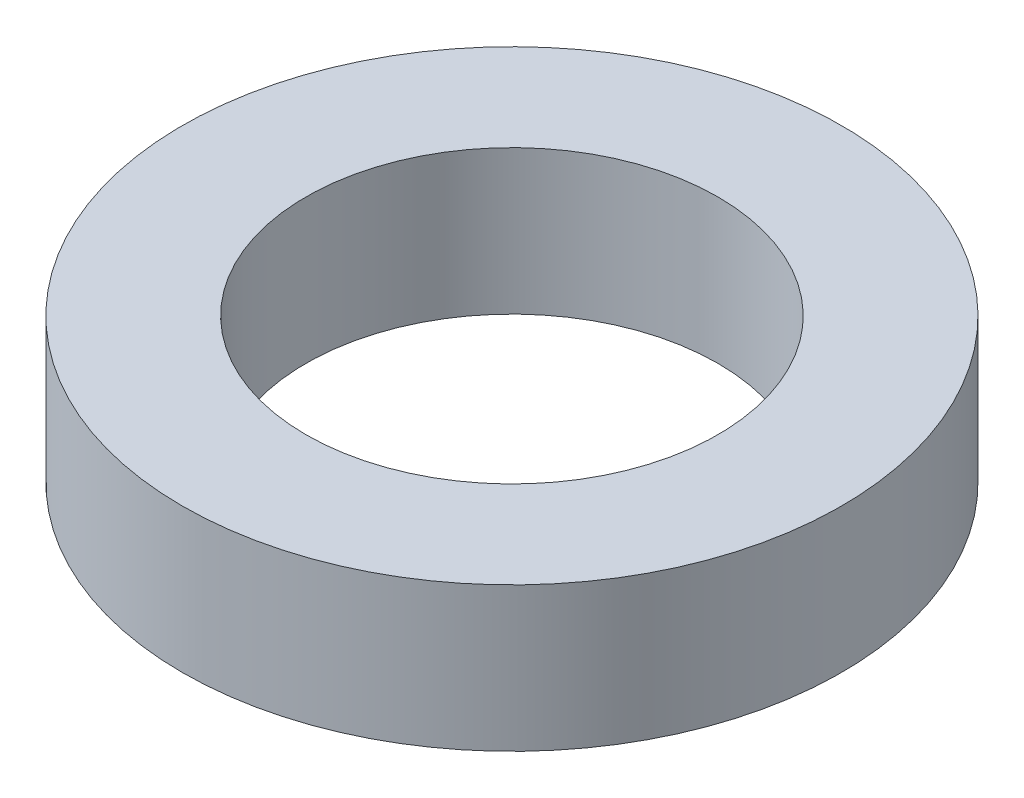
SolidWorks part; units mm, degrees
ref_plane "Front Plane" through (0, 0, 0) normal (0, 0, 1) x (1, 0, 0)
ref_plane "Top Plane" through (0, 0, 0) normal (0, 1, 0) x (1, 0, 0)
ref_plane "Right Plane" through (0, 0, 0) normal (1, 0, 0) x (0, 0, -1)
sketch "Sketch1" plane through (0, 0, 0) normal (0, 1, 0) x (1, 0, 0)
  circle A0 centre (0, 0) radius 16
  circle A1 centre (0, 0) radius 10
  dimension "D1" = 20
  dimension "D2" = 32
extrude "Boss-Extrude1" add sketch "Sketch1" along normal mid plane 7
equation "\"Ns\" = 48"
equation "\"Np_b\" = 40"
equation "\"Np_s\" = 28"
equation "\"Nr_b\" = 128"
equation "\"num_planet\" = 4"
equation "\"module\" = 0.7"
equation "\"fw_p_b\" = 29.99577312706301"
equation "\"fw_r_b\" = 29.99577312706301"
equation "\"fw_s_calc\" = 5.685933367726717"
equation "\"fw_r_s\" = 24.412913082891553"
equation "\"fw_p_s\" = 25.912913082891553"
equation "\"fw_s_used\" = 63.40868620995457"
equation "\"pressure_angle\" = 20.0"
equation "\"motor_OD\" = 106.8"
equation "\"motor_height\" = 47.6"
equation "\"motor_mount_hole_PCD\" = 40"
equation "\"motor_mount_hole_dia\" = 5"
equation "\"motor_mount_hole_num\" = 4"
equation "\"wire_slot_dist_from_center\" = 45.5"
equation "\"wire_slot_length\" = 10"
equation "\"wire_slot_radius\" = 3"
equation "\"motor_output_hole_PCD\" = 23"
equation "\"motor_output_hole_dia\" = 4"
equation "\"motor_output_hole_num\" = 4"
equation "\"h_a\" = 0.7"
equation "\"h_f\" = 0.875"
equation "\"clr_tip_root\" = 0.17500000000000004"
equation "\"dp_r_b\" = 89.6"
equation "\"db_r_b\" = 84.19645882241738"
equation "\"alpha_r_b\" = 0.8539582918412556"
equation "\"beta_r_b\" = 3.114166583682511"
equation "\"bearing_ID\" = 70"
equation "\"bearing_OD\" = 90"
equation "\"bearing_height\" = 10"
equation "\"clearance_planet\" = 1.5"
equation "\"case_dist\" = 6.5"
equation "\"Motor_case_OD_max\" = 131.3"
equation "\"case_mounting_PCD\" = 123.8"
equation "\"bearing mount thickness\" = 8"
equation "\"case_mounting_hole_dia\" = 3"
equation "\"output_mounting_PCD\" = 98"
equation "\"output_mounting_hole_dia\" = 4"
equation "\"clearance_case_mount_holes_shell_thickness\" = 1"
equation "\"motor_case_OD_base\" = 121.8"
equation "\"sec_carrier_thickness\" = 5"
equation "\"sun_coupler_hub_thickness\" = 4"
equation "\"clearance_sun_coupler_sec_carrier\" = 1.5"
equation "\"clearance_motor_and_case\" = 5"
equation "\"Motor_case_thickness\" = 2.5"
equation "\"Motor_case_ID\" = 116.8"
equation "\"case_mounting_hole_shift\" = 1.0"
equation "\"output_mounting_nut_wrench_size\" = 7"
equation "\"output_mounting_nut_thickness\" = 3.2"
equation "\"case_mounting_hole_allen_socket_dia\" = 5.5"
equation "\"output_mounting_nut_depth\" = 3"
equation "\"case_mounting_bolt_depth\" = 4.5"
equation "\"ring_radial_thickness\" = 5"
equation "\"ring_OD_b\" = 99.6"
equation "\"ring_to_chamfer_clearance\" = 1.5"
equation "\"Motor_case_OD_base_to_chamfer\" = 5"
equation "\"pattern_offset_from_motor_case_OD_base\" = 3"
equation "\"pattern_bulge_dia\" = 3"
equation "\"pattern_num_bulge\" = 18"
equation "\"pattern_depth\" = 2"
equation "\"case_mounting_wrench_size\" = 5.5"
equation "\"case_mounting_nut_clearance\" = 2"
equation "\"base_plate_thickness\" = 4"
equation "\"case_mounting_nut_thickness\" = 2.4"
equation "\"case_mounting_surface_height\" = 4"
equation "\"central_hole_offset_from_motor_mount_PCD\" = 5"
equation "\"driver_upper_holes_dist_from_center\" = 29"
equation "\"driver_lower_holes_dist_from_center\" = 13"
equation "\"driver_side_holes_dist_from_center\" = 22.5"
equation "\"driver_mount_holes_dia\" = 3"
equation "\"driver_mount_inserts_OD\" = 4.8"
equation "\"driver_mount_thickness\" = 1.5"
equation "\"driver_mount_height\" = 6"
equation "\"air_flow_hole_offset\" = 3"
equation "\"pressure angle\" = 20.0"
equation "\"h_b\" = 0.875"
equation "\"planet_pin_bolt_dia\" = 5"
equation "\"planet_pin_socket_head_dia\" = 8.5"
equation "\"carrier_PCD\" = 61.599999999999994"
equation "\"planet_shaft_dia\" = 8"
equation "\"planet_shaft_step_offset\" = 1"
equation "\"carrier_trapezoidal_support_sun_offset\" = 5"
equation "\"carrier_trapezoidal_support_hole_PCD_offset_bearing_ID\" = 4"
equation "\"carrier_trapezoidal_support_hole_dia\" = 3"
equation "\"carrier_trapezoidal_support_hole_socket_head_dia\" = 5.5"
equation "\"carrier_bearing_step_width\" = 1.5"
equation "\"standard_clearance_1_5mm\" = 1.5"
equation "\"standard_fillet_1_5mm\" = 1.5"
equation "\"sun_shaft_bearing_ID\" = 8"
equation "\"sun_shaft_bearing_OD\" = 16"
equation "\"sun_shaft_bearing_width\" = 5"
equation "\"standard_bearing_insertion_chamfer\" = 0.5"
equation "\"carrier_trapezoidal_support_hole_wrench_size\" = 5.5"
equation "\"planet_pin_bolt_wrench_size\" = 8"
equation "\"planet_bearing_OD\" = 12"
equation "\"planet_bearing_width\" = 3.5"
equation "\"planet_bore\" = 10"
equation "\"dp_s\" = 33.599999999999994"
equation "\"db_s\" = 31.57367205840652"
equation "\"alpha_s\" = 0.8539582918412343"
equation "\"beta_s\" = 2.0420834163175314"
equation "\"dp_p_b\" = 28.0"
equation "\"db_p_b\" = 26.311393382005434"
equation "\"alpha_p_b\" = 0.8539582918412485"
equation "\"beta_p_b\" = 2.792083416317503"
equation "\"sun_hub_dia\" = 30.0"
equation "\"sun_central_bolt_dia\" = 5"
equation "\"sun_central_bolt_socket_head_dia\" = 8.5"
equation "\"motor_output_hole_CSK_OD\" = 8"
equation "\"motor_output_hole_CSK_head_height\" = 2.0"
equation "\"bearing_retainer_thickness\" = 2"
equation "\"dp_p_s\" = 19.599999999999998"
equation "\"db_p_s\" = 18.417975367403802"
equation "\"alpha_p_s\" = 0.8539582918412592"
equation "\"beta_p_s\" = 4.7206548448889105"
equation "\"Nr_s\" = 116"
equation "\"clr_tip_root_s\" = 0.17500000000000004"
equation "\"dp_r_s\" = 81.19999999999999"
equation "\"db_r_s\" = 76.30304080781575"
equation "\"alpha_r_s\" = 0.8539582918412556"
equation "\"beta_r_s\" = 3.259640721613546"
equation "\"small_ring_case_thickness\" = 4"
equation "\"carrier_thickness\" = 4"
equation "\"small_ring_output_wall_thickness\" = 5"
equation "\"small_ring_output_wall_to_bearing_shaft_attachement_hole_dia\" = 4"
equation "\"small_ring_output_wall_to_bearing_shaft_attachement_hole_depth\" = 6.5"
equation "\"small_ring_output_wall_to_bearing_shaft_attachement_nut_wrench\" = 7"
equation "\"small_ring_output_wall_to_bearing_shaft_attachement_nut_thickness\" = 3.2"
equation "\"small_ring_output_wall_to_bearing_shaft_attachement_hole_pcd\" = 12"
equation "\"small_ring_output_wall_to_bearing_shaft_attachement_hole_num\" = 3"
equation "\"small_ring_output_wall_to_bearing_shaft_attachement_hole_CSK_OD\" = 8"
equation "\"small_ring_output_wall_to_bearing_shaft_attachement_hole_CSK_head_height\" = 2.0"
equation "\"carrier_small_ring_inner_bearing_ID\" = 20"
equation "\"carrier_small_ring_inner_bearing_OD\" = 32"
equation "\"carrier_small_ring_inner_bearing_height\" = 7"
equation "\"carrier_small_ring_inner_bearing_flap\" = 2"
equation "\"D1@Boss-Extrude1\"=\"carrier_small_ring_inner_bearing_height\""
equation "\"D1@Sketch1\"=\"carrier_small_ring_inner_bearing_ID\""
equation "\"D2@Sketch1\"=\"carrier_small_ring_inner_bearing_OD\""
